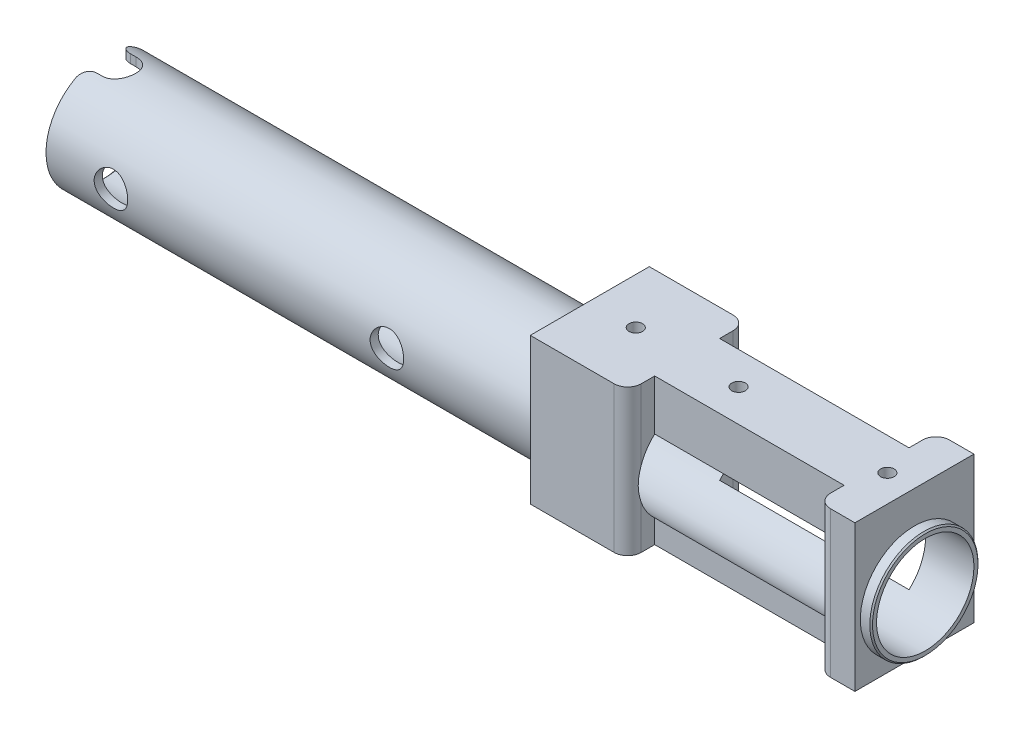
SolidWorks part; units mm, degrees
ref_plane "前视基准面" through (0, 0, 0) normal (0, 0, 1) x (1, 0, 0)
ref_plane "上视基准面" through (0, 0, 0) normal (0, 1, 0) x (1, 0, 0)
ref_plane "右视基准面" through (0, 0, 0) normal (1, 0, 0) x (0, 0, -1)
sketch "草图1" plane through (0, 0, 0) normal (1, 0, 0) x (0, 0, -1)
  line L1 (-11, 13.5) -> (11, 13.5)
  line L2 (-11, 13.5) -> (-11, -13.5)
  line L3 (-11, -13.5) -> (11, -13.5)
  line L4 (11, 13.5) -> (11, -13.5)
  line L5 (-11, 13.5) -> (11, -13.5) construction
  line L6 (-11, -13.5) -> (11, 13.5) construction
  point P0 (0, 0)
  dimension "D1" = 22
  dimension "D2" = 27
extrude "凸台-拉伸1" add sketch "草图1" along normal blind 152
sketch "草图2" plane through (152, 0, 0) normal (1, 0, 0) x (0, 0, -1)
  line L0 (-11, -13.5) -> (11, -13.5) construction
  circle A0 centre (0, -2.5) radius 9
  dimension "D1" = 18
  dimension "D2" = 11
extrude "切除-拉伸1" cut sketch "草图2" against normal blind 152
sketch "草图3" plane through (152, 0, 0) normal (1, 0, 0) x (0, 0, -1)
  line L1 (-13.0995, 18.8406) -> (13.0995, 18.8406)
  line L2 (-13.0995, 18.8406) -> (-13.0995, -15.121)
  line L3 (-13.0995, -15.121) -> (13.0995, -15.121)
  line L4 (13.0995, 18.8406) -> (13.0995, -15.121)
  line L5 (-13.0995, 18.8406) -> (13.0995, -15.121) construction
  line L6 (-13.0995, -15.121) -> (13.0995, 18.8406) construction
  circle A0 centre (0, -2.5) radius 10
  point P3 (0, 1.8598)
  dimension "D1" = 20
extrude "切除-拉伸2" cut sketch "草图3" against normal blind 2
sketch "草图4" plane through (0, 0, 0) normal (-1, 0, 0) x (0, 0, 1)
  line L1 (-13.5846, 20.9592) -> (13.5846, 20.9592)
  line L2 (-13.5846, 20.9592) -> (-13.5846, -16.3016)
  line L3 (-13.5846, -16.3016) -> (13.5846, -16.3016)
  line L4 (13.5846, 20.9592) -> (13.5846, -16.3016)
  line L5 (-13.5846, 20.9592) -> (13.5846, -16.3016) construction
  line L6 (-13.5846, -16.3016) -> (13.5846, 20.9592) construction
  circle A0 centre (0, -2.5) radius 10.5
  point P3 (0, 2.3288)
  dimension "D1" = 21
extrude "切除-拉伸3" cut sketch "草图4" against normal blind 90
sketch "草图5" plane through (0, 13.5, 0) normal (0, 1, 0) x (1, 0, 0)
  line L3 (108, 6) -> (143, 6)
  line L5 (108, -6) -> (143, -6)
  line L9 (131.8001, -6) -> (143, -16.6663) construction
  line L10 (108, 16.6663) -> (143, 16.6663)
  line L11 (108, 16.6663) -> (108, 6)
  line L12 (108, -16.6663) -> (143, -16.6663)
  line L13 (143, 16.6663) -> (143, 6)
  line L14 (108, 16.6663) -> (119.1999, 6) construction
  line L15 (108, -16.6663) -> (119.1999, -6) construction
  line L16 (131.8001, 6) -> (143, 16.6663) construction
  line L17 (143, -6) -> (143, -16.6663)
  line L18 (108, -6) -> (108, -16.6663)
  point P5 (125.5, 0)
  point P12 (125.5, 0)
  dimension "D1" = 12
  dimension "D3" = 35
extrude "切除-拉伸4" cut sketch "草图5" against normal blind 90
fillet "圆角2" radius 2.5 5 edges at (143, 0, -11) (108, 0, -11) (143, -11.3541, 6) (143, 0, 11) (108, 0, 11)
chamfer "倒角1" distance 0.5 angle 45 1 edges at (0, -2.5, -9)
sketch "草图6" plane through (0, 0, 0) normal (0, 1, 0) x (1, 0, 0)
  line L0 (6.1, 0) -> (8.5131, 0) construction
  line L1 (0, 10.5) -> (0, -10.5) construction
  line L2 (0, 10.5) -> (0, 3.1)
  line L3 (3, 3.1) -> (0, 3.1)
  line L4 (3, -3.1) -> (0, -3.1)
  line L5 (0, 3.1) -> (0, -3.1)
  line L6 (0, -3.1) -> (0, -10.5)
  arc A1 (3, -3.1) -> (3, 3.1) centre (3, 0) ccw
extrude "切除-拉伸5" cut sketch "草图6" along normal blind 21 contours L4 A1 L3 L5 region at (2.7614, 0, 0)
fillet "圆角3" radius 2 2 edges at (0, 7.006, 3.1) (0, 7.006, -3.1)
sketch "草图7" plane through (0, 0, 11) normal (0, 0, 1) x (1, 0, 0)
  line L0 (90, -2.5) -> (-4.9365, -2.5) construction
  line L1 (90, 8) -> (90, -13) construction
  line L2 (0, 6.6782) -> (0, -13) construction
  line L3 (90, -13.5) -> (90, 13.5) construction
  circle A0 centre (12, -2.5) radius 3.1
  circle A1 centre (63, -2.5) radius 3.1
  dimension "D1" = 6.2
  dimension "D2" = 6.2
  dimension "D4" = 51
  dimension "D5" = 78
  dimension "D3" = 12
extrude "切除-拉伸6" cut sketch "草图7" against normal through all both and the other way through all
sketch "草图8" plane through (0, 13.5, 0) normal (0, 1, 0) x (1, 0, 0)
  line L0 (90, 0) -> (145.9188, 0) construction
  line L1 (90, -11) -> (90, 11) construction
  line L2 (90, 10.5) -> (90, -10.5) construction
  line L3 (108, 6) -> (143, 6) construction
  line L4 (108, 6) -> (143, 6) construction
  line L5 (125.5, 6) -> (125.5, 0) construction
  point P5 (98.5, 0)
  point P6 (117.5, 0)
  point P7 (145, 0)
  dimension "D1" = 8.5
  dimension "D2" = 19
  dimension "D3" = 27.5
  dimension "D4" = 19.5
hole_wizard "M3 螺纹孔1" positions "草图9" profile "草图10" tap size "M3" standard "GB"
sketch "草图9" plane through (0, 13.5, 0) normal (0, 1, 0) x (1, 0, 0)
  point P0 (98.5, 0)
  point P3 (117.5, 0)
  point P6 (145, 0)
sketch "草图10" plane through (98.5, 13.5, 0) normal (1, 0, 0) x (0, 0, 1)
  line L0 (0, 0) -> (0, 5.7511)
  line L1 (0, 5.7511) -> (1.25, 5)
  line L2 (1.25, 5) -> (1.25, 0)
  line L5 (1.25, 0) -> (0, 0)
  line L10 (0, 5.7511) -> (-1.25, 5) construction
  line L11 (0, -6.35) -> (0, 107.95) construction
  dimension "螺纹孔钻头直径" = 2.5
  dimension "螺纹孔钻头深度" = 5
  dimension "导头角度" = 118
cosmetic thread "孔螺蚊线1" parameters "D1"=4, "D2"=3
cosmetic thread "孔螺蚊线2" parameters "D1"=4, "D2"=3
cosmetic thread "孔螺蚊线3" parameters "D1"=4, "D2"=3
chamfer "倒角2" distance 0.25 angle 45 1 edges at (152, -2.5, -10)
sketch "草图11" plane through (0, -13.5, 0) normal (0, -1, 0) x (1, 0, 0)
  line L0 (90, 0) -> (145.9188, 0) construction
  line L1 (148, 9) -> (92, 9) construction
  line L2 (148, 9) -> (148, -9) construction
  line L3 (148, -9) -> (92, -9) construction
  line L4 (92, 9) -> (92, -9) construction
  line L5 (148, 9) -> (92, -9) construction
  line L6 (148, -9) -> (92, 9) construction
  line L7 (105.5, 11) -> (90, 11) construction
  line L8 (90, -11) -> (90, 11) construction
  line L10 (150, 11) -> (150, -11) construction
  point P0 (120, 0)
  dimension "D1" = 2
  dimension "D2" = 2
  dimension "D3" = 2
  dimension "D4" = 56
hole_wizard "M3 螺纹孔2" positions "草图12" profile "草图13" tap size "M3" standard "GB"
sketch "草图12" plane through (0, -13.5, 0) normal (0, -1, 0) x (-1, 0, 0)
  point P0 (-92, -9)
  point P3 (-92, 9)
  point P6 (-148, 9)
  point P9 (-148, -9)
sketch "草图13" plane through (92, -13.5, 9) normal (1, 0, 0) x (0, 0, -1)
  line L0 (0, 0) -> (0, 5.7511)
  line L1 (0, 5.7511) -> (1.25, 5)
  line L2 (1.25, 5) -> (1.25, 0)
  line L5 (1.25, 0) -> (0, 0)
  line L10 (0, 5.7511) -> (-1.25, 5) construction
  line L11 (0, -6.35) -> (0, 107.95) construction
  dimension "螺纹孔钻头直径" = 2.5
  dimension "螺纹孔钻头深度" = 5
  dimension "导头角度" = 118
cosmetic thread "孔螺蚊线4" parameters "D1"=5, "D2"=3
cosmetic thread "孔螺蚊线5" parameters "D1"=5, "D2"=3
cosmetic thread "孔螺蚊线6" parameters "D1"=5, "D2"=3
cosmetic thread "孔螺蚊线7" parameters "D1"=5, "D2"=3
